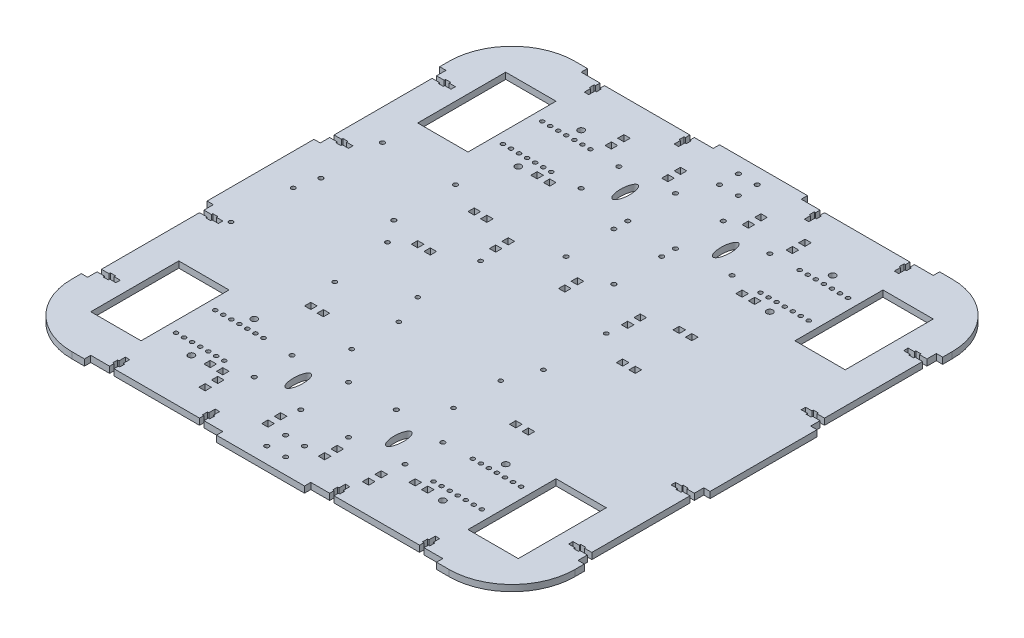
SolidWorks part; units mm, degrees
ref_plane "Front Plane" through (0, 0, 0) normal (0, 0, 1) x (1, 0, 0)
ref_plane "Top Plane" through (0, 0, 0) normal (0, 1, 0) x (1, 0, 0)
ref_plane "Right Plane" through (0, 0, 0) normal (1, 0, 0) x (0, 0, -1)
sketch "Sketch1" plane through (0, 0, 0) normal (0, 1, 0) x (1, 0, 0)
  line L0 (0, -1000) -> (0, 49000) construction
  line L1 (-170, 165) -> (-130, 165)
  line L2 (-170, 165) -> (-170, 95)
  line L3 (-170, 95) -> (-130, 95)
  line L4 (-130, 165) -> (-130, 95)
  line L5 (170, 95) -> (130, 95)
  line L6 (130, 165) -> (130, 95)
  line L7 (170, 165) -> (130, 165)
  line L8 (170, 165) -> (170, 95)
  line L9 (-1000, 0) -> (49000, 0) construction
  line L10 (-10, 190) -> (10, 190)
  line L11 (-10, 190) -> (-10, 170)
  line L12 (-10, 170) -> (10, 170)
  line L13 (10, 190) -> (10, 170)
  line L14 (-1010, 180) -> (48990, 180) construction
  line L15 (-1010, -180) -> (48990, -180) construction
  line L16 (0, 1000) -> (0, -49000) construction
  line L17 (-10, -170) -> (10, -170)
  line L18 (10, -190) -> (10, -170)
  line L19 (-10, -190) -> (10, -190)
  line L20 (-10, -190) -> (-10, -170)
  line L21 (170, -165) -> (170, -95)
  line L22 (-200, 200) -> (200, 200)
  line L23 (-200, 200) -> (-200, -200)
  line L24 (-200, -200) -> (200, -200)
  line L25 (200, 200) -> (200, -200)
  line L26 (170, -165) -> (130, -165)
  line L27 (130, -165) -> (130, -95)
  line L28 (170, -95) -> (130, -95)
  line L29 (-170, -95) -> (-130, -95)
  line L30 (-130, -165) -> (-130, -95)
  line L31 (-170, -165) -> (-130, -165)
  line L32 (-170, -165) -> (-170, -95)
  circle A0 centre (0, 0) radius 200 construction
  circle A1 centre (-7.5, 187.5) radius 1.75
  circle A2 centre (7.5, 187.5) radius 1.75
  circle A3 centre (7.5, 172.5) radius 1.75
  circle A4 centre (-7.5, 172.5) radius 1.75
  circle A5 centre (7.5, -187.5) radius 1.75
  circle A6 centre (-7.5, -187.5) radius 1.75
  circle A7 centre (-7.5, -172.5) radius 1.75
  circle A8 centre (7.5, -172.5) radius 1.75
  circle A9 centre (0, 0) radius 282.8427 construction
  point P8 (-150, 165)
  point P19 (0, 190)
  point P22 (-10, 180)
  dimension "D1" = 400
  dimension "D7" = 3.5
  dimension "D11" = 565.6854
  dimension "D2" = 40
  dimension "D3" = 70
  dimension "D4" = 150
  dimension "D5" = 20
  dimension "D6" = 180
  dimension "D8" = 2.5
  dimension "D9" = 2.5
  dimension "D10" = 35
extrude "Boss-Extrude2" add sketch "Sketch1" along normal blind 5 contours L25 L22 L23 L24 L1 L4 L3 L2 L7 L8 L5 L6 L10 L13 L12 L11 L19 L20 L17 L18 | L20 L19 L18 L17 A6 A5 A7 A8 | L13 L10 L11 L12 A2 A1 A3 A4 region at (0, 0, -180) region at (0, 0, 180) region at (0, 0, 0)
fillet "Fillet1" radius 50 4 edges at (200, 2.5, -200) (200, 2.5, 200) (-200, 2.5, 200) (-200, 2.5, -200)
sketch "Sketch2" plane through (0, 5, 0) normal (0, 1, 0) x (1, 0, 0)
  line L0 (-1094.0419, 130) -> (48905.9581, 130) construction
  line L1 (-130, 148.8) -> (-78.5, 148.8) construction
  line L2 (-130, 148.8) -> (-130, 111.2) construction
  line L3 (-130, 111.2) -> (-78.5, 111.2) construction
  line L4 (-78.5, 148.8) -> (-78.5, 111.2) construction
  line L5 (-130, 165) -> (-130, 95) construction
  line L6 (-170, 165) -> (-170, 95) construction
  line L7 (0, -1000) -> (0, 49000) construction
  line L8 (130, 111.2) -> (78.5, 111.2) construction
  line L9 (78.5, 148.8) -> (78.5, 111.2) construction
  line L10 (130, 148.8) -> (78.5, 148.8) construction
  line L11 (130, 148.8) -> (130, 111.2) construction
  line L12 (-1000, 0) -> (49000, 0) construction
  line L13 (130, -148.8) -> (130, -111.2) construction
  line L14 (130, -148.8) -> (78.5, -148.8) construction
  line L15 (78.5, -148.8) -> (78.5, -111.2) construction
  line L16 (130, -111.2) -> (78.5, -111.2) construction
  line L17 (-78.5, -148.8) -> (-78.5, -111.2) construction
  line L18 (-130, -111.2) -> (-78.5, -111.2) construction
  line L19 (-130, -148.8) -> (-130, -111.2) construction
  line L20 (-130, -148.8) -> (-78.5, -148.8) construction
  line L21 (-1094.0419, -130) -> (48905.9581, -130) construction
  circle A0 centre (-121.6, 145.6) radius 1.6
  circle A1 centre (-115.2, 145.6) radius 1.6
  circle A2 centre (-108.8, 145.6) radius 1.6
  circle A3 centre (-102.4, 145.6) radius 1.6
  circle A4 centre (-96, 145.6) radius 1.6
  circle A5 centre (-89.6, 145.6) radius 1.6
  circle A6 centre (-83.2, 145.6) radius 1.6
  circle A7 centre (-83.2, 114.4) radius 1.6
  circle A8 centre (-89.6, 114.4) radius 1.6
  circle A9 centre (-96, 114.4) radius 1.6
  circle A10 centre (-102.4, 114.4) radius 1.6
  circle A11 centre (-108.8, 114.4) radius 1.6
  circle A12 centre (-115.2, 114.4) radius 1.6
  circle A13 centre (-121.6, 114.4) radius 1.6
  circle A14 centre (83.2, 114.4) radius 1.6
  circle A15 centre (89.6, 114.4) radius 1.6
  circle A16 centre (96, 114.4) radius 1.6
  circle A17 centre (102.4, 114.4) radius 1.6
  circle A18 centre (108.8, 114.4) radius 1.6
  circle A19 centre (115.2, 114.4) radius 1.6
  circle A20 centre (121.6, 114.4) radius 1.6
  circle A21 centre (83.2, 145.6) radius 1.6
  circle A22 centre (89.6, 145.6) radius 1.6
  circle A23 centre (96, 145.6) radius 1.6
  circle A24 centre (102.4, 145.6) radius 1.6
  circle A25 centre (108.8, 145.6) radius 1.6
  circle A26 centre (115.2, 145.6) radius 1.6
  circle A27 centre (121.6, 145.6) radius 1.6
  circle A28 centre (121.6, -145.6) radius 1.6
  circle A29 centre (115.2, -145.6) radius 1.6
  circle A30 centre (108.8, -145.6) radius 1.6
  circle A31 centre (102.4, -145.6) radius 1.6
  circle A32 centre (96, -145.6) radius 1.6
  circle A33 centre (89.6, -145.6) radius 1.6
  circle A34 centre (83.2, -145.6) radius 1.6
  circle A35 centre (121.6, -114.4) radius 1.6
  circle A36 centre (115.2, -114.4) radius 1.6
  circle A37 centre (108.8, -114.4) radius 1.6
  circle A38 centre (102.4, -114.4) radius 1.6
  circle A39 centre (96, -114.4) radius 1.6
  circle A40 centre (89.6, -114.4) radius 1.6
  circle A41 centre (83.2, -114.4) radius 1.6
  circle A42 centre (-121.6, -114.4) radius 1.6
  circle A43 centre (-115.2, -114.4) radius 1.6
  circle A44 centre (-108.8, -114.4) radius 1.6
  circle A45 centre (-102.4, -114.4) radius 1.6
  circle A46 centre (-96, -114.4) radius 1.6
  circle A47 centre (-89.6, -114.4) radius 1.6
  circle A48 centre (-83.2, -114.4) radius 1.6
  circle A49 centre (-83.2, -145.6) radius 1.6
  circle A50 centre (-89.6, -145.6) radius 1.6
  circle A51 centre (-96, -145.6) radius 1.6
  circle A52 centre (-102.4, -145.6) radius 1.6
  circle A53 centre (-108.8, -145.6) radius 1.6
  circle A54 centre (-115.2, -145.6) radius 1.6
  circle A55 centre (-121.6, -145.6) radius 1.6
  point P9 (-130, 130)
  point P40 (-170, 130)
  dimension "D3" = 3.2
  dimension "D7" = 6.4
  dimension "D5" = 8.4
  dimension "D1" = 37.6
  dimension "D2" = 4.7
  dimension "D4" = 31.2
  dimension "D6" = 7
extrude "Cut-Extrude1" cut sketch "Sketch2" against normal blind 5
sketch "Sketch3" plane through (0, 5, 0) normal (0, 1, 0) x (1, 0, 0)
  line L0 (-150, -200) -> (150, -200) construction
  line L1 (-190, 3.34) -> (-88.4, 3.34) construction
  line L2 (-190, 3.34) -> (-190, -50) construction
  line L3 (-190, -50) -> (-88.4, -50) construction
  line L4 (-88.4, 3.34) -> (-88.4, -50) construction
  line L5 (-200, 150) -> (-200, -150) construction
  circle A0 centre (-176.03, -47.46) radius 1.65
  circle A1 centre (-174.76, 0.8) radius 1.65
  circle A2 centre (-93.48, -47.46) radius 1.65
  circle A3 centre (-99.83, 0.8) radius 1.65
  dimension "D5" = 3.3
  dimension "D8" = 3.3
  dimension "D9" = 96.52
  dimension "D10" = 90.17
  dimension "D1" = 101.6
  dimension "D2" = 53.34
  dimension "D3" = 13.97
  dimension "D4" = 2.54
  dimension "D6" = 15.24
  dimension "D7" = 50.8
  dimension "D11" = 150
  dimension "D12" = 10
extrude "Cut-Extrude2" cut sketch "Sketch3" against normal blind 10 contours A1 | A2 | L2 L1 L4 L3 | A0 | A3 region at (-174.76, 5, -0.8) region at (-93.48, 5, 47.46)
sketch "Sketch4" plane through (0, 5, 0) normal (0, 1, 0) x (1, 0, 0)
  line L0 (-19, 149) -> (19, 149) construction
  line L1 (-1149.7342, 130) -> (48850.2658, 130) construction
  line L2 (-22, 152) -> (22, 152) construction
  line L3 (-22, 152) -> (-22, 108) construction
  line L4 (-22, 108) -> (22, 108) construction
  line L5 (22, 152) -> (22, 108) construction
  line L6 (-19, 111) -> (19, 111) construction
  line L7 (-19, 100) -> (19, 100) construction
  line L8 (-1231.3219, 81) -> (48768.6781, 81) construction
  line L9 (-22, 103) -> (22, 103) construction
  line L10 (-22, 103) -> (-22, 59) construction
  line L11 (-22, 59) -> (22, 59) construction
  line L12 (22, 103) -> (22, 59) construction
  line L13 (-19, 62) -> (19, 62) construction
  line L14 (-19, -149) -> (19, -149) construction
  line L15 (-22, -152) -> (22, -152) construction
  line L16 (-130, 165) -> (-130, 95) construction
  line L17 (-150, 200) -> (150, 200) construction
  line L18 (22, -108) -> (22, -152) construction
  line L19 (-22, -108) -> (-22, -152) construction
  line L20 (-19, -111) -> (19, -111) construction
  line L21 (-22, -108) -> (22, -108) construction
  line L22 (-1022, -130) -> (48978, -130) construction
  line L23 (-130, -165) -> (-130, -95) construction
  circle A0 centre (-19, 149) radius 1.75
  circle A1 centre (19, 149) radius 1.75
  circle A2 centre (19, 111) radius 1.75
  circle A3 centre (-19, 111) radius 1.75
  circle A4 centre (-19, 100) radius 1.75
  circle A5 centre (19, 100) radius 1.75
  circle A6 centre (19, 62) radius 1.75
  circle A7 centre (-19, 62) radius 1.75
  circle A8 centre (-19, -149) radius 1.75
  circle A9 centre (19, -149) radius 1.75
  circle A10 centre (-19, -111) radius 1.75
  circle A11 centre (19, -111) radius 1.75
  point P9 (0, 149)
  point P10 (0, 152)
  point P14 (-22, 130)
  point P26 (0, 100)
  point P27 (0, 103)
  point P31 (-22, 81)
  point P38 (-130, 130)
  point P39 (0, 200)
  point P40 (0, 108)
  point P56 (-22, -130)
  point P58 (-130, -130)
  dimension "D1" = 3.5
  dimension "D5" = 3.5
  dimension "D2" = 38
  dimension "D3" = 44
  dimension "D4" = 38
  dimension "D6" = 38
  dimension "D7" = 44
  dimension "D8" = 38
  dimension "D9" = 5
  dimension "D10" = 2
extrude "Cut-Extrude3" cut sketch "Sketch4" against normal blind 10
sketch "Sketch5" plane through (0, 5, 0) normal (0, 1, 0) x (1, 0, 0)
  line L0 (-1136.3236, 43) -> (48863.6764, 43) construction
  line L1 (-174, 15) -> (-89, 15) construction
  line L2 (-174, 15) -> (-174, 71) construction
  line L3 (-174, 71) -> (-89, 71) construction
  line L4 (-89, 15) -> (-89, 71) construction
  line L5 (-180, 10) -> (-83, 10) construction
  line L6 (-180, 10) -> (-180, 76) construction
  line L7 (-180, 76) -> (-83, 76) construction
  line L8 (-83, 10) -> (-83, 76) construction
  line L9 (-200, 150) -> (-200, -150) construction
  line L10 (-150, -200) -> (150, -200) construction
  circle A0 centre (-170.5, 67.5) radius 1.75
  circle A1 centre (-112.5, 67.5) radius 1.75
  circle A2 centre (-112.5, 18.5) radius 1.75
  circle A3 centre (-170.5, 18.5) radius 1.75
  dimension "D4" = 3.5
  dimension "D5" = 3.5
  dimension "D1" = 56
  dimension "D2" = 85
  dimension "D3" = 58
  dimension "D6" = 3.5
  dimension "D7" = 49
  dimension "D8" = 3.5
  dimension "D9" = 5
  dimension "D10" = 5
  dimension "D11" = 6
  dimension "D12" = 6
  dimension "D13" = 20
  dimension "D14" = 210
extrude "Cut-Extrude4" cut sketch "Sketch5" against normal blind 10
sketch "Sketch6" plane through (0, 5, 0) normal (0, 1, 0) x (1, 0, 0)
  line L0 (-130, 165) -> (-130, 95) construction
  line L1 (0, -800) -> (0, 49200) construction
  line L2 (-150, 200) -> (150, 200) construction
  line L3 (-1200, 0) -> (48800, 0) construction
  line L4 (-200, 150) -> (-200, -150) construction
  ellipse E0 centre (-40, 130) end of major axis (-40, 140) minor radius 3.75
  ellipse E1 centre (40, 130) end of major axis (40, 140) minor radius 3.75
  ellipse E2 centre (40, -130) end of major axis (40, -140) minor radius 3.75
  ellipse E3 centre (-40, -130) end of major axis (-40, -140) minor radius 3.75
  point P13 (-130, 130)
  point P14 (-200, 0)
  point P26 (0, 200)
  dimension "D1" = 90
  dimension "D2" = 20
  dimension "D3" = 7.5
extrude "Cut-Extrude5" cut sketch "Sketch6" against normal blind 10
sketch "Sketch7" plane through (0, 5, 0) normal (0, 1, 0) x (1, 0, 0)
  line L0 (0, -1008.1082) -> (0, 48991.8918) construction
  line L1 (-53, 28) -> (53, 28) construction
  line L2 (-53, 28) -> (-53, -28) construction
  line L3 (-53, -28) -> (53, -28) construction
  line L4 (53, 28) -> (53, -28) construction
  line L5 (-53, 28) -> (-47, 28) construction
  line L6 (-53, 28) -> (-53, 22) construction
  line L7 (-53, 22) -> (-47, 22) construction
  line L8 (-47, 28) -> (-47, 22) construction
  line L9 (-1053, 0) -> (48947, 0) construction
  line L10 (-150, -200) -> (150, -200) construction
  line L11 (-200, 150) -> (-200, -150) construction
  circle A1 centre (-50, 25) radius 1.65
  circle A2 centre (50, 25) radius 1.65
  circle A3 centre (50, -25) radius 1.65
  circle A4 centre (-50, -25) radius 1.65
  point P10 (-50, 22)
  point P15 (-47, 25)
  point P16 (0, 28)
  point P17 (-53, 0)
  point P25 (0, -200)
  point P28 (-200, 0)
  dimension "D3" = 3.3
  dimension "D1" = 106
  dimension "D2" = 56
  dimension "D5" = 6
  dimension "D6" = 6
extrude "Cut-Extrude6" cut sketch "Sketch7" against normal blind 10
sketch "Sketch8" plane through (0, 5, 0) normal (0, 1, 0) x (1, 0, 0)
  line L0 (0, -1046.6714) -> (0, 48953.3286) construction
  line L1 (-43.5, -46.5) -> (43.5, -46.5) construction
  line L2 (-43.5, -46.5) -> (-43.5, -90) construction
  line L3 (-43.5, -90) -> (43.5, -90) construction
  line L4 (43.5, -46.5) -> (43.5, -90) construction
  line L5 (-43.5, -46.5) -> (-37.5, -46.5) construction
  line L6 (-43.5, -46.5) -> (-43.5, -52.5) construction
  line L7 (-43.5, -52.5) -> (-37.5, -52.5) construction
  line L8 (-37.5, -46.5) -> (-37.5, -52.5) construction
  line L9 (-1043.5, -68.25) -> (48956.5, -68.25) construction
  line L10 (37.5, -46.5) -> (37.5, -52.5) construction
  line L11 (43.5, -52.5) -> (37.5, -52.5) construction
  line L12 (-150, -200) -> (150, -200) construction
  circle A0 centre (-40.5, -49.5) radius 1.65
  circle A1 centre (40.5, -49.5) radius 1.65
  circle A2 centre (40.5, -87) radius 1.65
  circle A3 centre (-40.5, -87) radius 1.65
  point P10 (-40.5, -52.5)
  point P11 (-37.5, -49.5)
  point P15 (0, -46.5)
  point P17 (-43.5, -68.25)
  point P28 (0, -200)
  dimension "D3" = 3.3
  dimension "D1" = 87
  dimension "D2" = 6
  dimension "D4" = 43.5
  dimension "D5" = 110
extrude "Cut-Extrude7" cut sketch "Sketch8" against normal blind 5
sketch "Sketch10" plane through (0, 5, 0) normal (0, 1, 0) x (1, 0, 0)
  line L0 (-150, -200) -> (150, -200) construction
  line L1 (-125, -200) -> (-121.5, -200)
  line L2 (-125, -200) -> (-125, -191.5)
  line L3 (-125, -182.5) -> (-121.5, -182.5)
  line L4 (-121.5, -200) -> (-121.5, -191.5)
  line L6 (-121.5, -187.5) -> (-120.4, -187.5)
  line L7 (-126.1, -187.5) -> (-125, -187.5)
  line L8 (-126.1, -187.5) -> (-126.1, -191.5)
  line L9 (-126.1, -191.5) -> (-125, -191.5)
  line L10 (-120.4, -187.5) -> (-120.4, -191.5)
  line L11 (-121.5, -191.5) -> (-120.4, -191.5)
  line L12 (-125, -187.5) -> (-125, -182.5)
  line L13 (-121.5, -187.5) -> (-121.5, -182.5)
  line L14 (-125, -187.5) -> (-121.5, -187.5) construction
  line L15 (-121.5, -191.5) -> (-125, -191.5) construction
  line L16 (-53.5, -200) -> (-50, -200)
  line L17 (-50, -200) -> (-50, -191.5)
  line L18 (-50, -191.5) -> (-48.9, -191.5)
  line L19 (-48.9, -187.5) -> (-48.9, -191.5)
  line L20 (-50, -187.5) -> (-48.9, -187.5)
  line L21 (-50, -187.5) -> (-50, -182.5)
  line L22 (-53.5, -182.5) -> (-50, -182.5)
  line L23 (-53.5, -187.5) -> (-53.5, -182.5)
  line L24 (-54.6, -187.5) -> (-53.5, -187.5)
  line L25 (-54.6, -187.5) -> (-54.6, -191.5)
  line L26 (-54.6, -191.5) -> (-53.5, -191.5)
  line L27 (-53.5, -200) -> (-53.5, -191.5)
  line L28 (-50, -191.5) -> (-53.5, -191.5) construction
  line L29 (-53.5, -187.5) -> (-50, -187.5) construction
  line L30 (0, -1200) -> (0, 48800) construction
  line L31 (-200, 150) -> (-200, -150) construction
  line L32 (121.5, -191.5) -> (125, -191.5) construction
  line L33 (125, -187.5) -> (121.5, -187.5) construction
  line L34 (125, -200) -> (125, -191.5)
  line L35 (126.1, -191.5) -> (125, -191.5)
  line L36 (126.1, -187.5) -> (126.1, -191.5)
  line L37 (126.1, -187.5) -> (125, -187.5)
  line L38 (125, -187.5) -> (125, -182.5)
  line L39 (125, -182.5) -> (121.5, -182.5)
  line L40 (121.5, -187.5) -> (121.5, -182.5)
  line L41 (121.5, -187.5) -> (120.4, -187.5)
  line L42 (120.4, -187.5) -> (120.4, -191.5)
  line L43 (121.5, -191.5) -> (120.4, -191.5)
  line L44 (121.5, -200) -> (121.5, -191.5)
  line L45 (125, -200) -> (121.5, -200)
  line L46 (53.5, -187.5) -> (50, -187.5) construction
  line L47 (50, -191.5) -> (53.5, -191.5) construction
  line L48 (53.5, -200) -> (53.5, -191.5)
  line L49 (54.6, -191.5) -> (53.5, -191.5)
  line L50 (54.6, -187.5) -> (54.6, -191.5)
  line L51 (54.6, -187.5) -> (53.5, -187.5)
  line L52 (53.5, -187.5) -> (53.5, -182.5)
  line L53 (53.5, -182.5) -> (50, -182.5)
  line L54 (50, -187.5) -> (50, -182.5)
  line L55 (50, -187.5) -> (48.9, -187.5)
  line L56 (48.9, -187.5) -> (48.9, -191.5)
  line L57 (50, -191.5) -> (48.9, -191.5)
  line L58 (50, -200) -> (50, -191.5)
  line L59 (53.5, -200) -> (50, -200)
  line L60 (-1000, 0) -> (49000, 0) construction
  line L61 (125, 200) -> (121.5, 200)
  line L62 (121.5, 200) -> (121.5, 191.5)
  line L63 (121.5, 191.5) -> (120.4, 191.5)
  line L64 (120.4, 187.5) -> (120.4, 191.5)
  line L65 (121.5, 187.5) -> (120.4, 187.5)
  line L66 (121.5, 187.5) -> (121.5, 182.5)
  line L67 (125, 182.5) -> (121.5, 182.5)
  line L68 (125, 187.5) -> (125, 182.5)
  line L69 (126.1, 187.5) -> (125, 187.5)
  line L70 (126.1, 187.5) -> (126.1, 191.5)
  line L71 (126.1, 191.5) -> (125, 191.5)
  line L72 (125, 200) -> (125, 191.5)
  line L73 (53.5, 200) -> (50, 200)
  line L74 (50, 200) -> (50, 191.5)
  line L75 (50, 191.5) -> (48.9, 191.5)
  line L76 (48.9, 187.5) -> (48.9, 191.5)
  line L77 (50, 187.5) -> (48.9, 187.5)
  line L78 (50, 187.5) -> (50, 182.5)
  line L79 (53.5, 182.5) -> (50, 182.5)
  line L80 (53.5, 187.5) -> (53.5, 182.5)
  line L81 (54.6, 187.5) -> (53.5, 187.5)
  line L82 (54.6, 187.5) -> (54.6, 191.5)
  line L83 (54.6, 191.5) -> (53.5, 191.5)
  line L84 (53.5, 200) -> (53.5, 191.5)
  line L85 (-53.5, 200) -> (-53.5, 191.5)
  line L86 (-54.6, 191.5) -> (-53.5, 191.5)
  line L87 (-54.6, 187.5) -> (-54.6, 191.5)
  line L88 (-54.6, 187.5) -> (-53.5, 187.5)
  line L89 (-53.5, 187.5) -> (-53.5, 182.5)
  line L90 (-53.5, 182.5) -> (-50, 182.5)
  line L91 (-50, 187.5) -> (-50, 182.5)
  line L92 (-50, 187.5) -> (-48.9, 187.5)
  line L93 (-48.9, 187.5) -> (-48.9, 191.5)
  line L94 (-50, 191.5) -> (-48.9, 191.5)
  line L95 (-50, 200) -> (-50, 191.5)
  line L96 (-53.5, 200) -> (-50, 200)
  line L97 (-125, 200) -> (-125, 191.5)
  line L98 (-126.1, 191.5) -> (-125, 191.5)
  line L99 (-126.1, 187.5) -> (-126.1, 191.5)
  line L100 (-126.1, 187.5) -> (-125, 187.5)
  line L101 (-125, 187.5) -> (-125, 182.5)
  line L102 (-125, 182.5) -> (-121.5, 182.5)
  line L103 (-121.5, 187.5) -> (-121.5, 182.5)
  line L104 (-121.5, 187.5) -> (-120.4, 187.5)
  line L105 (-120.4, 187.5) -> (-120.4, 191.5)
  line L106 (-121.5, 191.5) -> (-120.4, 191.5)
  line L107 (-121.5, 200) -> (-121.5, 191.5)
  line L108 (-125, 200) -> (-121.5, 200)
  point P11 (-123.25, -200)
  point P15 (-123.25, -191.5)
  point P16 (-123.25, -187.5)
  point P17 (-123.25, -182.5)
  point P33 (0, -200)
  dimension "D1" = 3.5
  dimension "D2" = 5.7
  dimension "D3" = 5
  dimension "D4" = 4
  dimension "D5" = 1.1
  dimension "D7" = 75
  dimension "D8" = 50
  dimension "D9" = 17.5
  dimension "D6" = 2
extrude "Cut-Extrude8" cut sketch "Sketch10" against normal blind 10
sketch "Sketch11" plane through (0, 5, 0) normal (0, 1, 0) x (1, 0, 0)
  line L0 (-150, -200) -> (-125, -200) construction
  line L1 (-140, -200) -> (-35, -200)
  line L2 (-140, -200) -> (-140, -195)
  line L3 (-140, -195) -> (-35, -195)
  line L4 (-35, -200) -> (-35, -195)
  line L5 (-50, -200) -> (-50, -191.5) construction
  line L6 (-125, -191.5) -> (-125, -200) construction
  line L7 (0, -1200) -> (0, 48800) construction
  line L8 (-50, -200) -> (50, -200) construction
  line L9 (-1200, 0) -> (48800, 0) construction
  line L10 (-200, 150) -> (-200, -150) construction
  line L11 (140, -195) -> (35, -195)
  line L12 (35, -200) -> (35, -195)
  line L13 (140, -200) -> (35, -200)
  line L14 (140, -200) -> (140, -195)
  line L15 (140, 200) -> (140, 195)
  line L16 (140, 200) -> (35, 200)
  line L17 (35, 200) -> (35, 195)
  line L18 (140, 195) -> (35, 195)
  line L19 (-140, 195) -> (-35, 195)
  line L20 (-35, 200) -> (-35, 195)
  line L21 (-140, 200) -> (-35, 200)
  line L22 (-140, 200) -> (-140, 195)
  point P15 (0, -200)
  point P20 (-200, 0)
  dimension "D1" = 5
  dimension "D2" = 15
  dimension "D3" = 15
extrude "Cut-Extrude9" cut sketch "Sketch11" against normal blind 10
sketch "Sketch12" plane through (0, 5, 0) normal (0, 1, 0) x (1, 0, 0)
  line L0 (-200, 150) -> (-200, -150) construction
  line L1 (-200, 135) -> (-189, 135)
  line L2 (-200, 135) -> (-200, 131.5)
  line L3 (-200, 131.5) -> (-189, 131.5)
  line L4 (-180, 135) -> (-180, 131.5)
  line L5 (-200, 53.5) -> (-189, 53.5)
  line L6 (-189, 131.5) -> (-189, 130.4)
  line L7 (-189, 136.1) -> (-185, 136.1)
  line L8 (-189, 136.1) -> (-189, 135)
  line L9 (-189, 130.4) -> (-185, 130.4)
  line L10 (-185, 136.1) -> (-185, 135)
  line L11 (-185, 131.5) -> (-185, 130.4)
  line L12 (-185, 135) -> (-180, 135)
  line L13 (-185, 131.5) -> (-180, 131.5)
  line L14 (-189, 135) -> (-189, 131.5) construction
  line L15 (-185, 131.5) -> (-185, 135) construction
  line L16 (-189, 54.6) -> (-189, 53.5)
  line L17 (-189, 54.6) -> (-185, 54.6)
  line L18 (-185, 54.6) -> (-185, 53.5)
  line L19 (-185, 53.5) -> (-180, 53.5)
  line L20 (-180, 53.5) -> (-180, 50)
  line L21 (-185, 50) -> (-180, 50)
  line L22 (-185, 50) -> (-185, 48.9)
  line L23 (-189, 48.9) -> (-185, 48.9)
  line L24 (-189, 50) -> (-189, 48.9)
  line L25 (-200, 50) -> (-189, 50)
  line L26 (-200, 53.5) -> (-200, 50)
  line L27 (-1200, 0) -> (48800, 0) construction
  line L28 (-200, -53.5) -> (-200, -50)
  line L29 (-200, -50) -> (-189, -50)
  line L30 (-189, -50) -> (-189, -48.9)
  line L31 (-189, -48.9) -> (-185, -48.9)
  line L32 (-185, -50) -> (-185, -48.9)
  line L33 (-185, -50) -> (-180, -50)
  line L34 (-180, -53.5) -> (-180, -50)
  line L35 (-185, -53.5) -> (-180, -53.5)
  line L36 (-185, -54.6) -> (-185, -53.5)
  line L37 (-189, -54.6) -> (-185, -54.6)
  line L38 (-189, -54.6) -> (-189, -53.5)
  line L39 (-200, -53.5) -> (-189, -53.5)
  line L40 (-200, -135) -> (-200, -131.5)
  line L41 (-200, -131.5) -> (-189, -131.5)
  line L42 (-189, -131.5) -> (-189, -130.4)
  line L43 (-189, -130.4) -> (-185, -130.4)
  line L44 (-185, -131.5) -> (-185, -130.4)
  line L45 (-185, -131.5) -> (-180, -131.5)
  line L46 (-180, -135) -> (-180, -131.5)
  line L47 (-185, -135) -> (-180, -135)
  line L48 (-185, -136.1) -> (-185, -135)
  line L49 (-189, -136.1) -> (-185, -136.1)
  line L50 (-189, -136.1) -> (-189, -135)
  line L51 (-200, -135) -> (-189, -135)
  line L52 (0, -1200) -> (0, 48800) construction
  line L53 (-35, -200) -> (35, -200) construction
  line L54 (200, -135) -> (189, -135)
  line L55 (189, -136.1) -> (189, -135)
  line L56 (189, -136.1) -> (185, -136.1)
  line L57 (185, -136.1) -> (185, -135)
  line L58 (185, -135) -> (180, -135)
  line L59 (180, -135) -> (180, -131.5)
  line L60 (185, -131.5) -> (180, -131.5)
  line L61 (185, -131.5) -> (185, -130.4)
  line L62 (189, -130.4) -> (185, -130.4)
  line L63 (189, -131.5) -> (189, -130.4)
  line L64 (200, -131.5) -> (189, -131.5)
  line L65 (200, -135) -> (200, -131.5)
  line L66 (200, -53.5) -> (189, -53.5)
  line L67 (189, -54.6) -> (189, -53.5)
  line L68 (189, -54.6) -> (185, -54.6)
  line L69 (185, -54.6) -> (185, -53.5)
  line L70 (185, -53.5) -> (180, -53.5)
  line L71 (180, -53.5) -> (180, -50)
  line L72 (185, -50) -> (180, -50)
  line L73 (185, -50) -> (185, -48.9)
  line L74 (189, -48.9) -> (185, -48.9)
  line L75 (189, -50) -> (189, -48.9)
  line L76 (200, -50) -> (189, -50)
  line L77 (200, -53.5) -> (200, -50)
  line L78 (200, 53.5) -> (200, 50)
  line L79 (200, 50) -> (189, 50)
  line L80 (189, 50) -> (189, 48.9)
  line L81 (189, 48.9) -> (185, 48.9)
  line L82 (185, 50) -> (185, 48.9)
  line L83 (185, 50) -> (180, 50)
  line L84 (180, 53.5) -> (180, 50)
  line L85 (185, 53.5) -> (180, 53.5)
  line L86 (185, 54.6) -> (185, 53.5)
  line L87 (189, 54.6) -> (185, 54.6)
  line L88 (189, 54.6) -> (189, 53.5)
  line L89 (200, 53.5) -> (189, 53.5)
  line L90 (200, 135) -> (200, 131.5)
  line L91 (200, 131.5) -> (189, 131.5)
  line L92 (189, 131.5) -> (189, 130.4)
  line L93 (189, 130.4) -> (185, 130.4)
  line L94 (185, 131.5) -> (185, 130.4)
  line L95 (185, 131.5) -> (180, 131.5)
  line L96 (180, 135) -> (180, 131.5)
  line L97 (185, 135) -> (180, 135)
  line L98 (185, 136.1) -> (185, 135)
  line L99 (189, 136.1) -> (185, 136.1)
  line L100 (189, 136.1) -> (189, 135)
  line L101 (200, 135) -> (189, 135)
  point P31 (-200, 0)
  point P60 (0, -200)
  dimension "D1" = 20
  dimension "D2" = 3.5
  dimension "D3" = 5.7
  dimension "D4" = 5
  dimension "D5" = 4
  dimension "D6" = 15
  dimension "D7" = 1.1
  dimension "D9" = 50
  dimension "D8" = 2
extrude "Cut-Extrude10" cut sketch "Sketch12" against normal blind 5
sketch "Sketch13" plane through (0, 5, 0) normal (0, 1, 0) x (1, 0, 0)
  line L0 (-200, 150) -> (-200, 135) construction
  line L1 (-200, 142.5) -> (-195, 142.5)
  line L2 (-200, 142.5) -> (-200, 42.5)
  line L3 (-200, 42.5) -> (-195, 42.5)
  line L4 (-195, 142.5) -> (-195, 42.5)
  line L6 (-200, 50) -> (-189, 50) construction
  line L7 (-1200, 0) -> (48800, 0) construction
  line L8 (-200, 50) -> (-200, -50) construction
  line L9 (0, -800) -> (0, 49200) construction
  line L10 (-35, 200) -> (35, 200) construction
  line L11 (-200, -42.5) -> (-195, -42.5)
  line L12 (-195, -142.5) -> (-195, -42.5)
  line L13 (-200, -142.5) -> (-195, -142.5)
  line L14 (-200, -142.5) -> (-200, -42.5)
  line L15 (0, 800) -> (0, -49200) construction
  line L16 (200, -142.5) -> (200, -42.5)
  line L17 (200, -142.5) -> (195, -142.5)
  line L18 (195, -142.5) -> (195, -42.5)
  line L19 (200, -42.5) -> (195, -42.5)
  line L20 (200, 42.5) -> (195, 42.5)
  line L21 (195, 142.5) -> (195, 42.5)
  line L22 (200, 142.5) -> (195, 142.5)
  line L23 (200, 142.5) -> (200, 42.5)
  point P13 (-200, 0)
  point P18 (0, 200)
  dimension "D1" = 7.5
  dimension "D2" = 5
extrude "Cut-Extrude11" cut sketch "Sketch13" against normal blind 5
sketch "Sketch14" plane through (0, 5, 0) normal (0, 1, 0) x (1, 0, 0)
  line L0 (34, 164) -> (29, 164)
  line L1 (34, 154) -> (29, 154)
  line L2 (34, 154) -> (34, 159)
  line L3 (34, 159) -> (29, 159)
  line L4 (29, 154) -> (29, 159)
  line L5 (34, 164) -> (34, 169)
  line L6 (34, 169) -> (29, 169)
  line L7 (29, 164) -> (29, 169)
  line L8 (69, 164) -> (64, 164)
  line L9 (69, 154) -> (64, 154)
  line L10 (69, 154) -> (69, 159)
  line L11 (69, 159) -> (64, 159)
  line L12 (64, 154) -> (64, 159)
  line L13 (69, 164) -> (69, 169)
  line L14 (69, 169) -> (64, 169)
  line L15 (64, 164) -> (64, 169)
  line L16 (5, 47) -> (0, 47)
  line L17 (5, 37) -> (0, 37)
  line L18 (5, 37) -> (5, 42)
  line L19 (5, 42) -> (0, 42)
  line L20 (0, 37) -> (0, 42)
  line L21 (5, 47) -> (5, 52)
  line L22 (5, 52) -> (0, 52)
  line L23 (0, 47) -> (0, 52)
  line L24 (55, 47) -> (50, 47)
  line L25 (55, 37) -> (50, 37)
  line L26 (55, 37) -> (55, 42)
  line L27 (55, 42) -> (50, 42)
  line L28 (50, 37) -> (50, 42)
  line L29 (55, 47) -> (55, 52)
  line L30 (55, 52) -> (50, 52)
  line L31 (50, 47) -> (50, 52)
  line L32 (25, -164) -> (20, -164)
  line L33 (25, -174) -> (20, -174)
  line L34 (25, -174) -> (25, -169)
  line L35 (25, -169) -> (20, -169)
  line L36 (20, -174) -> (20, -169)
  line L37 (25, -164) -> (25, -159)
  line L38 (25, -159) -> (20, -159)
  line L39 (20, -164) -> (20, -159)
  line L40 (60, -164) -> (55, -164)
  line L41 (60, -174) -> (55, -174)
  line L42 (60, -174) -> (60, -169)
  line L43 (60, -169) -> (55, -169)
  line L44 (55, -174) -> (55, -169)
  line L45 (60, -164) -> (60, -159)
  line L46 (60, -159) -> (55, -159)
  line L47 (55, -164) -> (55, -159)
  line L48 (-30, 164) -> (-35, 164)
  line L49 (-30, 154) -> (-35, 154)
  line L50 (-30, 154) -> (-30, 159)
  line L51 (-30, 159) -> (-35, 159)
  line L52 (-35, 154) -> (-35, 159)
  line L53 (-30, 164) -> (-30, 169)
  line L54 (-30, 169) -> (-35, 169)
  line L55 (-35, 164) -> (-35, 169)
  line L56 (-50, 47) -> (-55, 47)
  line L57 (-50, 37) -> (-55, 37)
  line L58 (-50, 37) -> (-50, 42)
  line L59 (-50, 42) -> (-55, 42)
  line L60 (-55, 37) -> (-55, 42)
  line L61 (-50, 47) -> (-50, 52)
  line L62 (-50, 52) -> (-55, 52)
  line L63 (-55, 47) -> (-55, 52)
  line L64 (-20, -164) -> (-25, -164)
  line L65 (-20, -174) -> (-25, -174)
  line L66 (-20, -174) -> (-20, -169)
  line L67 (-20, -169) -> (-25, -169)
  line L68 (-25, -174) -> (-25, -169)
  line L69 (-20, -164) -> (-20, -159)
  line L70 (-20, -159) -> (-25, -159)
  line L71 (-25, -164) -> (-25, -159)
  line L72 (19, 62) -> (-19, 62) construction
  line L73 (19, 149) -> (-19, 149) construction
  line L74 (-75, 164) -> (-80, 164)
  line L75 (-75, 154) -> (-80, 154)
  line L76 (-75, 154) -> (-75, 159)
  line L77 (-75, 159) -> (-80, 159)
  line L78 (-80, 154) -> (-80, 159)
  line L79 (-75, 164) -> (-75, 169)
  line L80 (-75, 169) -> (-80, 169)
  line L81 (-80, 164) -> (-80, 169)
  line L82 (19, -149) -> (-19, -149) construction
  line L83 (-70, -164) -> (-75, -164)
  line L84 (-70, -174) -> (-75, -174)
  line L85 (-70, -174) -> (-70, -169)
  line L86 (-70, -169) -> (-75, -169)
  line L87 (-75, -174) -> (-75, -169)
  line L88 (-70, -164) -> (-70, -159)
  line L89 (-70, -159) -> (-75, -159)
  line L90 (-75, -164) -> (-75, -159)
  line L91 (79, -156) -> (74, -156)
  line L92 (89, -156) -> (84, -156)
  line L93 (89, -156) -> (89, -151)
  line L94 (89, -151) -> (84, -151)
  line L95 (84, -156) -> (84, -151)
  line L96 (79, -156) -> (79, -151)
  line L97 (79, -151) -> (74, -151)
  line L98 (74, -156) -> (74, -151)
  line L99 (79, -76) -> (74, -76)
  line L100 (89, -76) -> (84, -76)
  line L101 (89, -76) -> (89, -71)
  line L102 (89, -71) -> (84, -71)
  line L103 (84, -76) -> (84, -71)
  line L104 (79, -76) -> (79, -71)
  line L105 (79, -71) -> (74, -71)
  line L106 (74, -76) -> (74, -71)
  line L107 (79, 9) -> (74, 9)
  line L108 (89, 9) -> (84, 9)
  line L109 (89, 9) -> (89, 14)
  line L110 (89, 14) -> (84, 14)
  line L111 (84, 9) -> (84, 14)
  line L112 (79, 9) -> (79, 14)
  line L113 (79, 14) -> (74, 14)
  line L114 (74, 9) -> (74, 14)
  line L115 (79, 54) -> (74, 54)
  line L116 (89, 54) -> (84, 54)
  line L117 (89, 54) -> (89, 59)
  line L118 (89, 59) -> (84, 59)
  line L119 (84, 54) -> (84, 59)
  line L120 (79, 54) -> (79, 59)
  line L121 (79, 59) -> (74, 59)
  line L122 (74, 54) -> (74, 59)
  line L123 (79, 104) -> (74, 104)
  line L124 (89, 104) -> (84, 104)
  line L125 (89, 104) -> (89, 109)
  line L126 (89, 109) -> (84, 109)
  line L127 (84, 104) -> (84, 109)
  line L128 (79, 104) -> (79, 109)
  line L129 (79, 109) -> (74, 109)
  line L130 (74, 104) -> (74, 109)
  line L131 (0, -1200) -> (0, 48800) construction
  line L132 (-35, -200) -> (35, -200) construction
  line L133 (-79, 104) -> (-79, 109)
  line L134 (-79, 109) -> (-74, 109)
  line L135 (-74, 104) -> (-74, 109)
  line L136 (-79, 104) -> (-74, 104)
  line L137 (-89, 104) -> (-89, 109)
  line L138 (-89, 109) -> (-84, 109)
  line L139 (-84, 104) -> (-84, 109)
  line L140 (-89, 104) -> (-84, 104)
  line L141 (-79, 54) -> (-79, 59)
  line L142 (-79, 59) -> (-74, 59)
  line L143 (-74, 54) -> (-74, 59)
  line L144 (-79, 54) -> (-74, 54)
  line L145 (-89, 54) -> (-89, 59)
  line L146 (-89, 59) -> (-84, 59)
  line L147 (-84, 54) -> (-84, 59)
  line L148 (-89, 54) -> (-84, 54)
  line L149 (-79, 9) -> (-79, 14)
  line L150 (-79, 14) -> (-74, 14)
  line L151 (-74, 9) -> (-74, 14)
  line L152 (-79, 9) -> (-74, 9)
  line L153 (-89, 9) -> (-89, 14)
  line L154 (-89, 14) -> (-84, 14)
  line L155 (-84, 9) -> (-84, 14)
  line L156 (-89, 9) -> (-84, 9)
  line L157 (-79, -76) -> (-79, -71)
  line L158 (-79, -71) -> (-74, -71)
  line L159 (-74, -76) -> (-74, -71)
  line L160 (-79, -76) -> (-74, -76)
  line L161 (-89, -76) -> (-89, -71)
  line L162 (-89, -71) -> (-84, -71)
  line L163 (-84, -76) -> (-84, -71)
  line L164 (-89, -76) -> (-84, -76)
  line L165 (-79, -156) -> (-79, -151)
  line L166 (-79, -151) -> (-74, -151)
  line L167 (-74, -156) -> (-74, -151)
  line L168 (-79, -156) -> (-74, -156)
  line L169 (-89, -156) -> (-89, -151)
  line L170 (-89, -151) -> (-84, -151)
  line L171 (-84, -156) -> (-84, -151)
  line L172 (-89, -156) -> (-84, -156)
  circle A0 centre (19, 149) radius 1.75 construction
  point P78 (0, 49.5)
  point P79 (0, 62)
  point P83 (0, 149)
  point P84 (0, -149)
  point P151 (0, -200)
  dimension "D20" = 10
  dimension "D1" = 5
  dimension "D2" = 5
  dimension "D3" = 5
  dimension "D4" = 5
  dimension "D5" = 5
  dimension "D6" = 5
  dimension "D7" = 5
  dimension "D8" = 5
  dimension "D9" = 5
  dimension "D10" = 5
  dimension "D11" = 5
  dimension "D12" = 5
  dimension "D13" = 5
  dimension "D14" = 5
  dimension "D15" = 5
  dimension "D16" = 5
  dimension "D17" = 5
  dimension "D18" = 5
  dimension "D19" = 30
  dimension "D21" = 10
  dimension "D22" = 10
  dimension "D23" = 45
  dimension "D24" = 50
  dimension "D25" = 30
  dimension "D26" = 5
  dimension "D27" = 5
  dimension "D28" = 40
  dimension "D29" = 20
  dimension "D30" = 10
  dimension "D31" = 30
  dimension "D32" = 20
  dimension "D33" = 5
  dimension "D34" = 5
  dimension "D35" = 45
  dimension "D36" = 5
  dimension "D37" = 5
  dimension "D38" = 5
  dimension "D39" = 5
  dimension "D40" = 5
  dimension "D41" = 5
  dimension "D42" = 5
  dimension "D43" = 5
  dimension "D44" = 5
  dimension "D45" = 5
  dimension "D46" = 5
  dimension "D47" = 45
  dimension "D48" = 45
  dimension "D49" = 40
  dimension "D50" = 80
  dimension "D51" = 75
extrude "Cut-Extrude12" cut sketch "Sketch14" against normal blind 10
sketch "Sketch15" plane through (0, 5, 0) normal (0, 1, 0) x (1, 0, 0)
  line L0 (-1130, 130) -> (48870, 130) construction
  line L1 (-130, 165) -> (-130, 95) construction
  line L2 (0, -800) -> (0, 49200) construction
  line L3 (-35, 200) -> (35, 200) construction
  line L4 (-1200, 0) -> (48800, 0) construction
  line L5 (-200, 42.5) -> (-200, -42.5) construction
  line L6 (1200, 0) -> (-48800, 0) construction
  circle A0 centre (-100, 105) radius 2.5
  circle A1 centre (-100, 155) radius 2.5
  circle A2 centre (100, 155) radius 2.5
  circle A3 centre (100, 105) radius 2.5
  circle A4 centre (100, -105) radius 2.5
  circle A5 centre (100, -155) radius 2.5
  circle A6 centre (-100, -155) radius 2.5
  circle A7 centre (-100, -105) radius 2.5
  point P7 (-130, 130)
  point P14 (0, 200)
  point P19 (-200, 0)
  dimension "D1" = 5
  dimension "D2" = 25
  dimension "D3" = 30
extrude "Cut-Extrude13" cut sketch "Sketch15" against normal blind 10
sketch "Sketch16" plane through (0, 5, 0) normal (0, 1, 0) x (1, 0, 0)
  line L1 (-60, 145) -> (-60, 115) construction
  line L2 (-130, 165) -> (-130, 95) construction
  line L3 (0, -800) -> (0, 49200) construction
  line L4 (-35, 200) -> (35, 200) construction
  line L5 (-1200, 0) -> (48800, 0) construction
  line L6 (-200, 42.5) -> (-200, -42.5) construction
  circle A0 centre (-60, 145) radius 1.75
  circle A1 centre (-60, 115) radius 1.75
  circle A2 centre (60, 115) radius 1.75
  circle A3 centre (60, 145) radius 1.75
  circle A4 centre (60, -115) radius 1.75
  circle A5 centre (60, -145) radius 1.75
  circle A6 centre (-60, -145) radius 1.75
  circle A7 centre (-60, -115) radius 1.75
  ellipse E0 centre (-40, 130) end of major axis (-40, 140) minor radius 3.75 construction
  point P10 (-130, 130)
  point P13 (-60, 130)
  point P19 (0, 200)
  point P24 (-200, 0)
  dimension "D1" = 3.5
  dimension "D2" = 30
  dimension "D3" = 20
extrude "Cut-Extrude14" cut sketch "Sketch16" against normal blind 10
